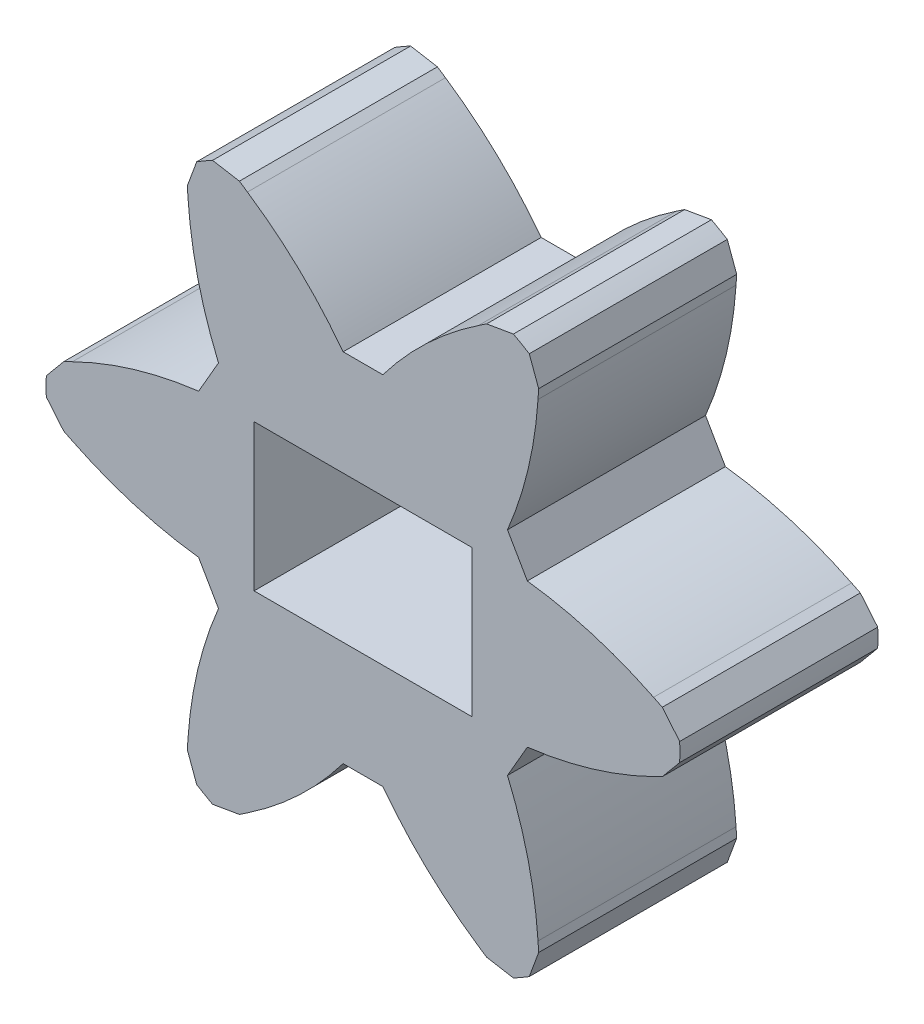
SolidWorks part; units mm, degrees
ref_plane "Front Plane" through (0, 0, 0) normal (0, 0, 1) x (1, 0, 0)
ref_plane "Top Plane" through (0, 0, 0) normal (0, 1, 0) x (1, 0, 0)
ref_plane "Right Plane" through (0, 0, 0) normal (1, 0, 0) x (0, 0, -1)
sketch "Sketch1" plane through (0, 0, 0) normal (0, 0, 1) x (1, 0, 0)
  line L0 (-2.75, 1.85) -> (2.75, 1.85)
  line L1 (1.2374, -1.2374) -> (-1.2374, -1.2374) construction
  line L2 (1.2374, -1.2374) -> (1.2374, 1.2374) construction
  line L3 (1.2374, 1.2374) -> (-1.2374, 1.2374) construction
  line L4 (-1.2374, -1.2374) -> (-1.2374, 1.2374) construction
  line L5 (1.2374, -1.2374) -> (-1.2374, 1.2374) construction
  line L6 (1.2374, 1.2374) -> (-1.2374, -1.2374) construction
  line L7 (2.75, 1.85) -> (2.75, -1.85)
  line L8 (2.75, -1.85) -> (-2.75, -1.85)
  line L9 (-2.75, -1.85) -> (-2.75, 1.85)
  circle A0 centre (0, 0) radius 8
  circle A1 centre (0, 0) radius 1.75 construction
  point P11 (0, 1.85)
  point P13 (-2.75, 0)
  dimension "D1" = 16
  dimension "D2" = 3.5
  dimension "D3" = 5.5
  dimension "D4" = 3.7
extrude "Boss-Extrude1" add sketch "Sketch1" along normal blind 5
sketch "Sketch2" plane through (0, 0, 0) normal (0, 0, 1) x (1, 0, 0)
  line L0 (0, 0) -> (0, 10.088) construction
  line L8 (-7.3319, 22.2218) -> (0, 24.9522)
  line L11 (-1.3301, 5.7236) -> (-3.121, 6.924)
  line L12 (-3.121, 6.924) -> (-3.7984, 7.0407)
  line L13 (-3.7984, 7.0407) -> (-7.3319, 22.2218)
  line L19 (-1.3301, 5.7236) -> (-0.5015, 4.5026)
  line L20 (-0.5015, 4.5026) -> (0.5015, 4.5026)
  line L21 (1.3301, 5.7236) -> (0.5015, 4.5026)
  line L22 (3.7984, 7.0407) -> (7.3319, 22.2218)
  line L23 (3.121, 6.924) -> (3.7984, 7.0407)
  line L24 (1.3301, 5.7236) -> (3.121, 6.924)
  line L25 (7.3319, 22.2218) -> (0, 24.9522)
  circle A14 centre (0, 0) radius 8 construction
  point P9 (0, 4.5026)
  point P16 (0, 8)
extrude "Cut-Extrude1" cut sketch "Sketch2" along normal through all
pattern_circular "CirPattern1" count 6 over 360 about axis through (0, 0, 5) along (0, 0, -1) of "Cut-Extrude1" reverse direction yes
sketch "Sketch3" plane through (0, 0, 0) normal (0, 0, 1) x (1, 0, 0)
  circle A0 centre (0, 0) radius 7.5
  dimension "D1" = 15
fillet "Fillet1" radius 10 12 edges at (-1.3301, -5.7236, 2.5) (5.6218, 1.7099, 2.5) (4.2918, -4.0137, 2.5) (5.6218, -1.7099, 2.5) (1.3301, -5.7236, 2.5) (-4.2918, -4.0137, 2.5) (-5.6218, -1.7099, 2.5) (-5.6218, 1.7099, 2.5) (-4.2918, 4.0137, 2.5) (4.2918, 4.0137, 2.5) (1.3301, 5.7236, 2.5) (-1.3301, 5.7236, 2.5)
chamfer "Chamfer1" distance 1 distance2 0.5 4 edges at (2.75, 0, 0) (0, -1.85, 0) (-2.75, 0, 0) (0, 1.85, 0) first distance on face at (2.75, 0, 2.5) first distance on face at (0, -1.85, 2.5) first distance on face at (-2.75, 0, 2.5) first distance on face at (0, 1.85, 2.5)
